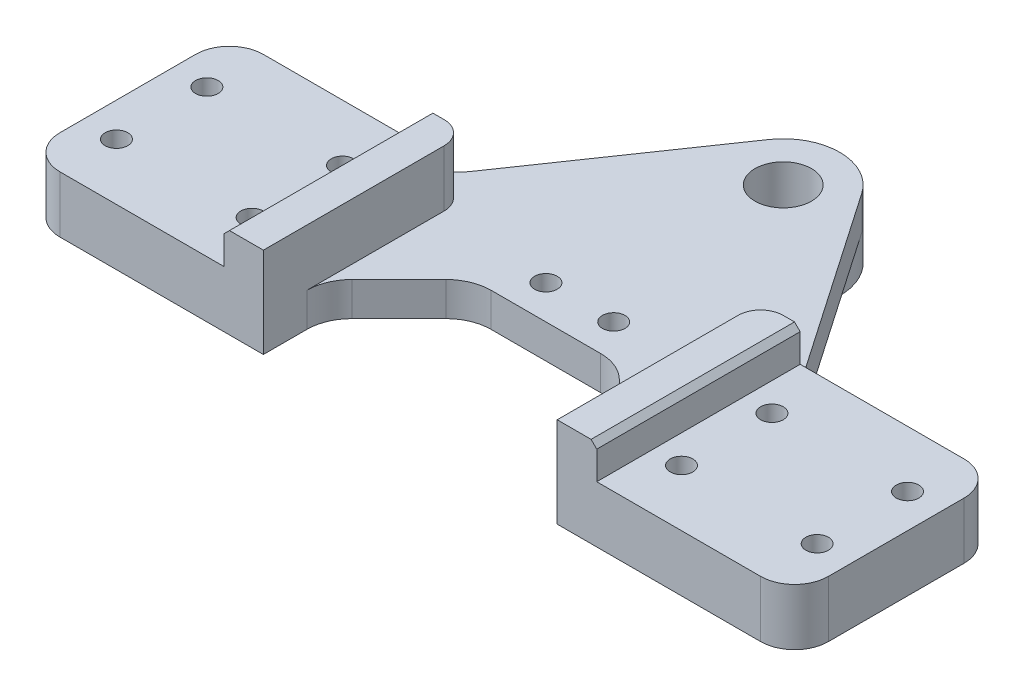
SolidWorks part; units mm, degrees
material "6063-T1"
ref_plane "前视基准面" through (0, 0, 0) normal (0, 0, 1) x (1, 0, 0)
ref_plane "上视基准面" through (0, 0, 0) normal (0, 1, 0) x (1, 0, 0)
ref_plane "右视基准面" through (0, 0, 0) normal (1, 0, 0) x (0, 0, -1)
sketch "草图1" plane through (0, 0, 0) normal (0, 1, 0) x (1, 0, 0)
  line L0 (-25, -24) -> (25, -24) construction
  line L1 (0, 0) -> (0, -24) construction
  line L2 (-34, -33) -> (-34, -15)
  line L3 (-31, -28) -> (-19, -28) construction
  line L4 (-31, -28) -> (-31, -20) construction
  line L5 (-31, -20) -> (-19, -20) construction
  line L6 (-19, -28) -> (-19, -20) construction
  line L7 (-31, -28) -> (-19, -20) construction
  line L8 (-31, -20) -> (-19, -28) construction
  line L9 (-34, -15) -> (-19, -15)
  line L10 (-14.8785, -12.8308) -> (-4.1215, 2.8308)
  line L11 (31, -28) -> (19, -28) construction
  line L12 (31, -20) -> (19, -28) construction
  line L13 (31, -28) -> (19, -20) construction
  line L14 (19, -28) -> (19, -20) construction
  line L15 (31, -20) -> (19, -20) construction
  line L16 (31, -28) -> (31, -20) construction
  line L17 (14.8785, -12.8308) -> (4.1215, 2.8308)
  line L18 (34, -15) -> (19, -15)
  line L19 (34, -33) -> (34, -15)
  line L20 (-34, -33) -> (-13, -33)
  line L21 (-13, -33) -> (-13, -27.5)
  line L22 (-6.5, -21) -> (6.5, -21)
  line L23 (-13, -27.5) -> (-6.5, -21)
  line L24 (13, -33) -> (13, -27.5)
  line L25 (34, -33) -> (13, -33)
  line L26 (6.5, -21) -> (13, -27.5)
  circle A0 centre (0, 0) radius 2.5
  arc A1 (4.1215, 2.8308) -> (-4.1215, 2.8308) centre (0, 0) ccw
  arc A2 (-19, -15) -> (-14.8785, -12.8308) centre (-19, -10) ccw
  circle A3 centre (-19, -20) radius 1
  circle A4 centre (-19, -28) radius 1
  circle A5 centre (-31, -28) radius 1
  circle A6 centre (-31, -20) radius 1
  circle A7 centre (31, -28) radius 1
  circle A8 centre (19, -28) radius 1
  circle A9 centre (31, -20) radius 1
  circle A10 centre (19, -20) radius 1
  arc A11 (19, -15) -> (14.8785, -12.8308) centre (19, -10) cw
  circle A12 centre (-3, -18) radius 1
  circle A13 centre (3, -18) radius 1
  dimension "D1" = 5
  dimension "D2" = 10
  dimension "D7" = 2
  dimension "D10" = 5
  dimension "D13" = 13
  dimension "D16" = 6
  dimension "D17" = 2
  dimension "D18" = 3
  dimension "D3" = 24
  dimension "D4" = 8
  dimension "D5" = 12
  dimension "D6" = 50
  dimension "D8" = 3
  dimension "D9" = 5
  dimension "D11" = 15
  dimension "D12" = 5
  dimension "D14" = 12
  dimension "D15" = 6
extrude "凸台-拉伸1" add sketch "草图1" along normal blind 3
sketch "草图2" plane through (0, 3, 0) normal (0, 1, 0) x (1, 0, 0)
  line L0 (-19, -15) -> (-34, -15) construction
  line L1 (13, -33) -> (16.5, -33)
  line L2 (13, -33) -> (13, -15)
  line L3 (13, -15) -> (16.5, -15)
  line L4 (16.5, -33) -> (16.5, -15)
  line L5 (-13, -33) -> (-16.5, -33)
  line L6 (-13, -33) -> (-13, -15)
  line L7 (-13, -15) -> (-16.5, -15)
  line L8 (-16.5, -33) -> (-16.5, -15)
  circle A0 centre (-19, -28) radius 1 construction
  dimension "D1" = 2.5
extrude "凸台-拉伸2" add sketch "草图2" along normal blind 5
sketch "草图5" plane through (0, 3, 0) normal (0, 1, 0) x (1, 0, 0)
  line L1 (16.5, -33) -> (34, -33)
  line L2 (16.5, -33) -> (16.5, -15)
  line L3 (16.5, -15) -> (34, -15)
  line L4 (34, -33) -> (34, -15)
  line L5 (-16.5, -33) -> (-34, -33)
  line L6 (-16.5, -33) -> (-16.5, -15)
  line L7 (-16.5, -15) -> (-34, -15)
  line L8 (-34, -33) -> (-34, -15)
  circle A0 centre (19, -28) radius 1 construction
  circle A1 centre (31, -28) radius 1 construction
  circle A2 centre (31, -20) radius 1 construction
  circle A3 centre (19, -20) radius 1 construction
  circle A4 centre (-31, -28) radius 1 construction
  circle A5 centre (-19, -28) radius 1 construction
  circle A6 centre (-19, -20) radius 1 construction
  circle A7 centre (-31, -20) radius 1 construction
  circle A8 centre (19, -28) radius 1
  circle A9 centre (31, -28) radius 1
  circle A10 centre (31, -20) radius 1
  circle A11 centre (19, -20) radius 1
  circle A12 centre (-31, -28) radius 1
  circle A13 centre (-19, -28) radius 1
  circle A14 centre (-19, -20) radius 1
  circle A15 centre (-31, -20) radius 1
extrude "凸台-拉伸4" add sketch "草图5" along normal blind 2
chamfer "倒角1" distance 0.5 angle 45 2 edges at (-16.5, 8, 24) (16.5, 8, 24)
fillet "圆角1" radius 3 4 edges at (-34, 2.5, 15) (-34, 2.5, 33) (34, 2.5, 15) (34, 2.5, 33)
sketch "草图3" plane through (0, 0, 0) normal (0, -1, 0) x (1, 0, 0)
  circle A0 centre (0, 0) radius 5
  circle A1 centre (0, 0) radius 2.5
  arc A2 (-4.1215, -2.8308) -> (4.1215, -2.8308) centre (0, 0) ccw construction
  circle A3 centre (0, 0) radius 2.5 construction
extrude "凸台-拉伸3" add sketch "草图3" along normal blind 3
fillet "圆角2" radius 2 2 edges at (-13, 5.5, 15) (13, 5.5, 15)
fillet "圆角3" radius 4 4 edges at (13, 1.5, 27.5) (6.5, 1.5, 21) (-13, 1.5, 27.5) (-6.5, 1.5, 21)
